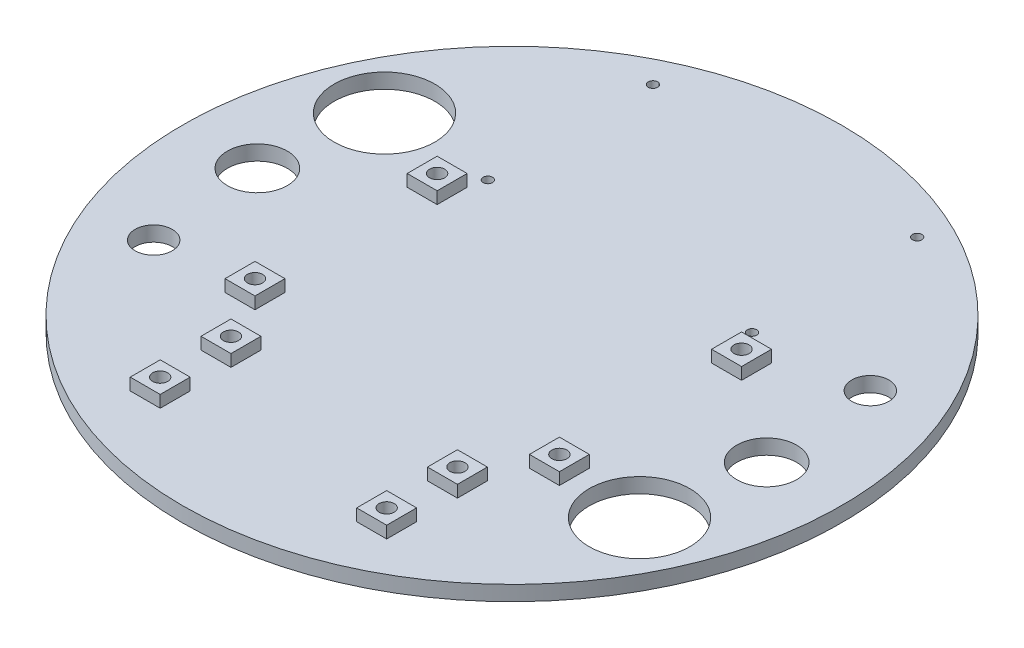
SolidWorks part; units mm, degrees
ref_plane "Front Plane" through (0, 0, 0) normal (0, 0, 1) x (1, 0, 0)
ref_plane "Top Plane" through (0, 0, 0) normal (0, 1, 0) x (1, 0, 0)
ref_plane "Right Plane" through (0, 0, 0) normal (1, 0, 0) x (0, 0, -1)
sketch "Sketch1" plane through (0, 0, 0) normal (0, 1, 0) x (1, 0, 0)
  line L0 (53.975, 0) -> (-53.975, 0) construction
  line L1 (0, 0) -> (-50.6445, 23.6159) construction
  line L2 (0, 0) -> (50.6445, -23.6159) construction
  line L3 (51.7955, 24.1526) -> (-51.7955, -24.1526) construction
  circle A0 centre (0, 0) radius 69.85
  circle A1 centre (-51.7955, -24.1526) radius 3.937
  circle A2 centre (-53.975, 0) radius 6.35
  circle A3 centre (-50.6445, 23.6159) radius 10.668
  circle A4 centre (51.7955, 24.1526) radius 3.937
  circle A5 centre (53.975, 0) radius 6.35
  circle A6 centre (50.6445, -23.6159) radius 10.668
  point P6 (0, 0)
  point P11 (0, 0)
extrude "Boss-Extrude1" add sketch "Sketch1" along normal blind 3.175
sketch "Sketch2" plane through (0, 3.175, 0) normal (0, 1, 0) x (1, 0, 0)
  line L1 (28.5773, 22.2989) -> (-27.4227, 22.2989) construction
  line L2 (28.5773, 22.2989) -> (28.5773, 57.2989) construction
  line L3 (28.5773, 57.2989) -> (-27.4227, 57.2989) construction
  line L4 (-27.4227, 22.2989) -> (-27.4227, 57.2989) construction
  line L5 (28.5773, 22.2989) -> (-27.4227, 57.2989) construction
  line L6 (28.5773, 57.2989) -> (-27.4227, 22.2989) construction
  line L11 (33.084, -23.0392) -> (-31.436, -23.0392) construction
  line L17 (33.084, -23.0392) -> (33.084, 15.5708) construction
  line L18 (33.084, 15.5708) -> (-31.436, 15.5708) construction
  line L29 (-31.436, -23.0392) -> (-31.436, 15.5708) construction
  line L30 (33.084, -23.0392) -> (-31.436, 15.5708) construction
  line L35 (33.084, 15.5708) -> (-31.436, -23.0392) construction
  line L36 (-28.261, 12.3958) -> (-34.611, 12.3958)
  line L45 (-28.261, 12.3958) -> (-28.261, 18.7458)
  line L46 (-28.261, 18.7458) -> (-34.611, 18.7458)
  line L51 (24.5954, -51.161) -> (-23.4046, -51.161) construction
  line L52 (24.5954, -51.161) -> (24.5954, -36.161) construction
  line L57 (24.5954, -36.161) -> (-23.4046, -36.161) construction
  line L58 (-23.4046, -51.161) -> (-23.4046, -36.161) construction
  line L63 (24.5954, -51.161) -> (-23.4046, -36.161) construction
  line L64 (24.5954, -36.161) -> (-23.4046, -51.161) construction
  line L65 (-20.2296, -39.336) -> (-26.5796, -39.336)
  line L66 (-20.2296, -39.336) -> (-20.2296, -32.986)
  line L67 (-20.2296, -32.986) -> (-26.5796, -32.986)
  line L68 (-26.5796, -39.336) -> (-26.5796, -32.986)
  line L69 (-20.2296, -39.336) -> (-26.5796, -32.986) construction
  line L70 (-20.2296, -32.986) -> (-26.5796, -39.336) construction
  line L71 (27.7704, -39.336) -> (21.4204, -39.336)
  line L72 (27.7704, -39.336) -> (27.7704, -32.986)
  line L73 (27.7704, -32.986) -> (21.4204, -32.986)
  line L74 (21.4204, -39.336) -> (21.4204, -32.986)
  line L75 (27.7704, -39.336) -> (21.4204, -32.986) construction
  line L76 (27.7704, -32.986) -> (21.4204, -39.336) construction
  line L77 (-20.2296, -54.336) -> (-26.5796, -54.336)
  line L78 (-20.2296, -54.336) -> (-20.2296, -47.986)
  line L79 (-20.2296, -47.986) -> (-26.5796, -47.986)
  line L80 (-26.5796, -54.336) -> (-26.5796, -47.986)
  line L81 (-20.2296, -54.336) -> (-26.5796, -47.986) construction
  line L82 (-20.2296, -47.986) -> (-26.5796, -54.336) construction
  line L83 (27.7704, -54.336) -> (21.4204, -54.336)
  line L84 (27.7704, -54.336) -> (27.7704, -47.986)
  line L85 (27.7704, -47.986) -> (21.4204, -47.986)
  line L86 (21.4204, -54.336) -> (21.4204, -47.986)
  line L87 (27.7704, -54.336) -> (21.4204, -47.986) construction
  line L88 (27.7704, -47.986) -> (21.4204, -54.336) construction
  line L89 (-34.611, 12.3958) -> (-34.611, 18.7458)
  line L90 (-28.261, 12.3958) -> (-34.611, 18.7458) construction
  line L91 (-28.261, 18.7458) -> (-34.611, 12.3958) construction
  line L92 (-28.261, -26.2142) -> (-34.611, -26.2142)
  line L93 (-28.261, -26.2142) -> (-28.261, -19.8642)
  line L94 (-28.261, -19.8642) -> (-34.611, -19.8642)
  line L95 (-34.611, -26.2142) -> (-34.611, -19.8642)
  line L96 (-28.261, -26.2142) -> (-34.611, -19.8642) construction
  line L97 (-28.261, -19.8642) -> (-34.611, -26.2142) construction
  line L102 (36.259, -26.2142) -> (29.909, -26.2142)
  line L103 (36.259, -26.2142) -> (36.259, -19.8642)
  line L104 (36.259, -19.8642) -> (29.909, -19.8642)
  line L105 (29.909, -26.2142) -> (29.909, -19.8642)
  line L106 (36.259, -26.2142) -> (29.909, -19.8642) construction
  line L107 (36.259, -19.8642) -> (29.909, -26.2142) construction
  line L108 (36.259, 12.3958) -> (29.909, 12.3958)
  line L109 (36.259, 12.3958) -> (36.259, 18.7458)
  line L110 (36.259, 18.7458) -> (29.909, 18.7458)
  line L111 (29.909, 12.3958) -> (29.909, 18.7458)
  line L112 (36.259, 12.3958) -> (29.909, 18.7458) construction
  line L113 (36.259, 18.7458) -> (29.909, 12.3958) construction
  circle A8 centre (-23.4046, -36.161) radius 1.6
  circle A9 centre (24.5954, -36.161) radius 1.6
  circle A10 centre (-23.4046, -51.161) radius 1.6
  circle A11 centre (24.5954, -51.161) radius 1.6
  circle A12 centre (-31.436, 15.5708) radius 1.6
  circle A13 centre (33.084, 15.5708) radius 1.6
  circle A14 centre (-31.436, -23.0392) radius 1.6
  circle A15 centre (33.084, -23.0392) radius 1.6
  point P0 (0.5773, 39.7989)
  point P5 (0.5954, -43.661)
  point P9 (0.824, -3.7342)
sketch "Sketch5" plane through (0, 3.175, 0) normal (0, 1, 0) x (1, 0, 0)
  circle A0 centre (-27.4227, 57.2989) radius 1
  circle A1 centre (28.5773, 57.2989) radius 1
  circle A2 centre (28.5773, 22.2989) radius 1
  circle A3 centre (-27.4227, 22.2989) radius 1
extrude "Cut-Extrude1" cut sketch "Sketch5" against normal blind 25.4
extrude "Cut-Extrude2" cut sketch "Sketch2" against normal blind 25.4 contours A13 | A12 | A14 | A15 | A10 | A11 | A9 | A8
extrude "Boss-Extrude2" add sketch "Sketch2<9>" along normal blind 2.54
sketch "Sketch2<9>" plane through (0, 3.175, 0) normal (0, 1, 0) x (1, 0, 0) same geometry as "Sketch2"
